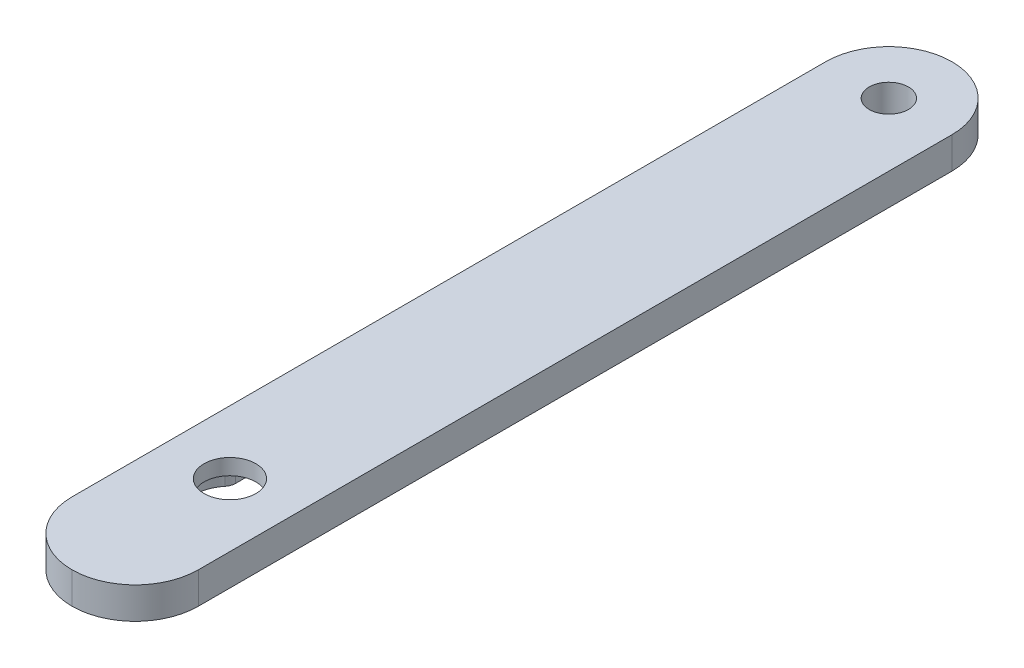
SolidWorks part; units mm, degrees
ref_plane "Front Plane" through (0, 0, 0) normal (0, 0, 1) x (1, 0, 0)
ref_plane "Top Plane" through (0, 0, 0) normal (0, 1, 0) x (1, 0, 0)
ref_plane "Right Plane" through (0, 0, 0) normal (1, 0, 0) x (0, 0, -1)
sketch "Sketch1" plane through (0, 0, 0) normal (0, 1, 0) x (1, 0, 0)
  line L0 (0, 0) -> (0, 12.7862) construction
  line L16 (-23.6152, 0) -> (23.6152, 0) construction
  line L22 (-3.8884, 4.0299) -> (-3.8884, 8.5053)
  line L23 (-3.8177, 9.3432) -> (-2.6646, 16.1267)
  line L24 (3.8299, 9.3786) -> (2.6768, 16.1621)
  line L25 (3.9006, 4.0181) -> (3.9006, 8.5407)
  line L26 (-3.8945, -4.024) -> (-3.8945, -8.5406)
  line L27 (-3.8238, -9.3786) -> (-2.6707, -16.1621)
  line L28 (3.8238, -9.3786) -> (2.6707, -16.1621)
  line L29 (3.8945, -4.024) -> (3.8945, -8.5406)
  line L30 (-10, 104.3) -> (-10, 25)
  line L31 (-7.5, 22.5) -> (7.5, 22.5)
  line L32 (-7.5, 22.5) -> (-7.5, -22.5)
  line L33 (-7.5, -22.5) -> (7.5, -22.5)
  line L34 (7.5, 22.5) -> (7.5, -22.5)
  line L35 (-7.5, 22.5) -> (7.5, -22.5) construction
  line L36 (-7.5, -22.5) -> (7.5, 22.5) construction
  line L41 (-10, 25) -> (10, 25)
  line L42 (-10, 25) -> (-10, -25)
  line L43 (-10, -25) -> (10, -25)
  line L44 (10, 25) -> (10, -25)
  line L45 (-10, 25) -> (10, 25)
  line L46 (-10, 25) -> (-10, 104.3)
  line L48 (10, 25) -> (10, 104.3)
  line L49 (10, 104.3) -> (10, 25)
  arc A8 (-2.5939, 16.9879) -> (2.606, 17) centre (0.006, 17) cw
  arc A9 (-2.6, -17) -> (2.6, -17) centre (0, -17) ccw
  circle A10 centre (0, 0) radius 5.6
  circle A11 centre (0, 0) radius 1.6
  circle A13 centre (0, 0) radius 4.1
  arc A14 (2.6, -17) -> (2.6707, -16.1621) centre (7.6, -17) cw
  arc A15 (-2.6707, -16.1621) -> (-2.6, -17) centre (-7.6, -17) cw
  arc A16 (-3.8945, -8.5406) -> (-3.8238, -9.3786) centre (1.1055, -8.5406) ccw
  arc A17 (3.8238, -9.3786) -> (3.8945, -8.5406) centre (-1.1055, -8.5406) ccw
  arc A18 (2.606, 17) -> (2.6768, 16.1621) centre (7.606, 17) ccw
  arc A19 (-2.6646, 16.1267) -> (-2.5939, 16.9879) centre (-7.5939, 16.9647) ccw
  arc A20 (3.8299, 9.3786) -> (3.9006, 8.5407) centre (-1.0994, 8.5407) cw
  arc A21 (-3.8884, 8.5053) -> (-3.8177, 9.3432) centre (1.1116, 8.5053) cw
  circle A22 centre (0, 104.3) radius 3.1
  arc A23 (-10, 104.3) -> (10, 104.3) centre (0, 104.3) cw
  point P14 (0, 0)
  point P49 (0, 19.6)
  point P50 (0, -19.6)
  dimension "D1" = 11.2
  dimension "D2" = 3.2
  dimension "D7" = 50
  dimension "D3" = 15
  dimension "D4" = 8.2
  dimension "D8" = 5
  dimension "D12" = 6.2
  dimension "D14" = 10
  dimension "D5" = 45
  dimension "D6" = 20
  dimension "D9" = 19.6
  dimension "D10" = 19.6
  dimension "D11" = 2.5
  dimension "D13" = 104.3
extrude "Boss-Extrude1" add sketch "Sketch1" against normal blind 2.2 contours L34 L31 L32 L33 A10 L29 L28 A9 L27 L26 L22 L23 A8 L24 L25 region at (0, 0, -22.0257)
extrude "Boss-Extrude2" add sketch "Sketch1<3>" against normal blind 2.5 contours L44 L41 L42 L43 L31 L34 L33 L32 | L34 L31 L32 L33 L22 A21 L23 A19 A8 A18 L24 A20 L25 A10 L29 A17 L28 A14 A9 A15 L27 A16 L26 region at (0, 0, -24.4615) region at (0, 0, -22.0257)
sketch "Sketch1<3>" plane through (0, 0, 0) normal (0, 1, 0) x (1, 0, 0) same geometry as "Sketch1"
extrude "Boss-Extrude3" add sketch "Sketch1<4>" along normal blind 2.5 contours L34 L31 L32 L33 A10 L29 L28 A9 L27 L26 L22 L23 A8 L24 L25 | A10 L25 L24 A8 L23 L22 | A10 L26 L27 A9 L28 L29 | L44 L41 L42 L43 L31 L34 L33 L32 | A10 A13 region at (0.0082, 0, -11.4698) region at (0.0082, 0, -5.4416) region at (0, 0, 11.4704) region at (0, 0, -24.4615) region at (0, 0, -22.0257)
sketch "Sketch1<4>" plane through (0, 0, 0) normal (0, 1, 0) x (1, 0, 0) same geometry as "Sketch1"
fillet "Fillet1" radius 2 4 edges at (3.8945, -1.25, 4.024) (-3.8945, -1.25, 4.024) (-3.8884, -1.25, -4.0299) (3.9006, -1.25, -4.0181)
extrude "Boss-Extrude4" add sketch "Sketch1<5>" along normal mid plane 5 contours A23 L30 L41 L48 A22 region at (0, 0, -67.9764)
sketch "Sketch1<5>" plane through (0, 0, 0) normal (0, 1, 0) x (1, 0, 0) same geometry as "Sketch1"
fillet "Fillet2" radius 10 2 edges at (10, 0, 25) (-10, 0, 25)
sketch "Sketch2" plane through (0, -2.5, 0) normal (0, -1, 0) x (1, 0, 0)
  line L0 (-2.8868, -83.7449) -> (-2.8868, -93.7449)
  line L1 (-2.8868, -93.7449) -> (5.7735, -88.7449)
  line L2 (5.7735, -88.7449) -> (-2.8868, -83.7449)
  line L6 (-2.8868, -83.7449) -> (1.4434, -91.2449) construction
  line L7 (5.7735, -88.7449) -> (-2.8868, -88.7449) construction
  line L8 (-2.8868, -93.7449) -> (1.4434, -86.2449) construction
  line L9 (-2.8868, -80.7449) -> (5.7735, -75.7449)
  line L10 (5.7735, -75.7449) -> (5.7735, -85.7449)
  line L11 (5.7735, -85.7449) -> (-2.8868, -80.7449)
  line L12 (-3.0868, -80.7449) -> (5.8735, -75.5717)
  line L13 (5.8735, -75.5717) -> (5.8735, -85.9181)
  line L14 (5.8735, -85.9181) -> (-3.0868, -80.7449)
  line L15 (5.9735, -88.7449) -> (-2.9868, -83.5717)
  line L16 (-2.9868, -83.5717) -> (-2.9868, -93.9181)
  line L17 (-2.9868, -93.9181) -> (5.9735, -88.7449)
  line L18 (5.7735, -72.7449) -> (-2.8868, -67.7449)
  line L19 (5.9735, -72.7449) -> (-2.9868, -67.5717)
  line L20 (-2.8868, -77.7449) -> (5.7735, -72.7449)
  line L21 (-2.9868, -77.9181) -> (5.9735, -72.7449)
  line L22 (-2.8868, -67.7449) -> (-2.8868, -77.7449)
  line L23 (-2.9868, -67.5717) -> (-2.9868, -77.9181)
  line L24 (5.7735, -56.7449) -> (-2.8868, -51.7449)
  line L25 (5.9735, -56.7449) -> (-2.9868, -51.5717)
  line L26 (-2.8868, -61.7449) -> (5.7735, -56.7449)
  line L27 (-2.9868, -61.9181) -> (5.9735, -56.7449)
  line L28 (-2.8868, -51.7449) -> (-2.8868, -61.7449)
  line L29 (-2.9868, -51.5717) -> (-2.9868, -61.9181)
  line L30 (5.7735, -40.7449) -> (-2.8868, -35.7449)
  line L31 (5.9735, -40.7449) -> (-2.9868, -35.5717)
  line L32 (-2.8868, -45.7449) -> (5.7735, -40.7449)
  line L33 (-2.9868, -45.9181) -> (5.9735, -40.7449)
  line L34 (-2.8868, -35.7449) -> (-2.8868, -45.7449)
  line L35 (-2.9868, -35.5717) -> (-2.9868, -45.9181)
  line L36 (5.7735, -24.7449) -> (-2.8868, -19.7449)
  line L37 (5.9735, -24.7449) -> (-2.9868, -19.5717)
  line L38 (-2.8868, -29.7449) -> (5.7735, -24.7449)
  line L39 (-2.9868, -29.9181) -> (5.9735, -24.7449)
  line L40 (-2.8868, -19.7449) -> (-2.8868, -29.7449)
  line L41 (-2.9868, -19.5717) -> (-2.9868, -29.9181)
  line L42 (-3.0868, -64.7449) -> (5.8735, -59.5717)
  line L43 (5.8735, -59.5717) -> (5.8735, -69.9181)
  line L44 (5.8735, -69.9181) -> (-3.0868, -64.7449)
  line L45 (5.7735, -69.7449) -> (-2.8868, -64.7449)
  line L46 (-2.8868, -64.7449) -> (5.7735, -59.7449)
  line L47 (5.7735, -59.7449) -> (5.7735, -69.7449)
  line L48 (-3.0868, -48.7449) -> (5.8735, -43.5717)
  line L49 (5.8735, -43.5717) -> (5.8735, -53.9181)
  line L50 (5.8735, -53.9181) -> (-3.0868, -48.7449)
  line L51 (5.7735, -53.7449) -> (-2.8868, -48.7449)
  line L52 (-2.8868, -48.7449) -> (5.7735, -43.7449)
  line L53 (5.7735, -43.7449) -> (5.7735, -53.7449)
  line L54 (-3.0868, -32.7449) -> (5.8735, -27.5717)
  line L55 (5.8735, -27.5717) -> (5.8735, -37.9181)
  line L56 (5.8735, -37.9181) -> (-3.0868, -32.7449)
  line L57 (5.7735, -37.7449) -> (-2.8868, -32.7449)
  line L58 (-2.8868, -32.7449) -> (5.7735, -27.7449)
  line L59 (5.7735, -27.7449) -> (5.7735, -37.7449)
  circle A0 centre (0, -104.3) radius 3.1 construction
  circle A1 centre (0, -104.3) radius 3.1
  point P12 (0, -88.7449)
  point P15 (5.7735, -80.7449)
  dimension "D1" = 10
  dimension "D2" = 10
  dimension "D3" = 10
  dimension "D4" = 10
  dimension "D5" = 10
  dimension "D6" = 10
  dimension "D7" = 3
  dimension "D8" = 0.1
  dimension "D9" = 0.1
  dimension "D10" = 5
  dimension "D11" = 4
extrude "Cut-Extrude1" cut sketch "Sketch2" against normal blind 4
